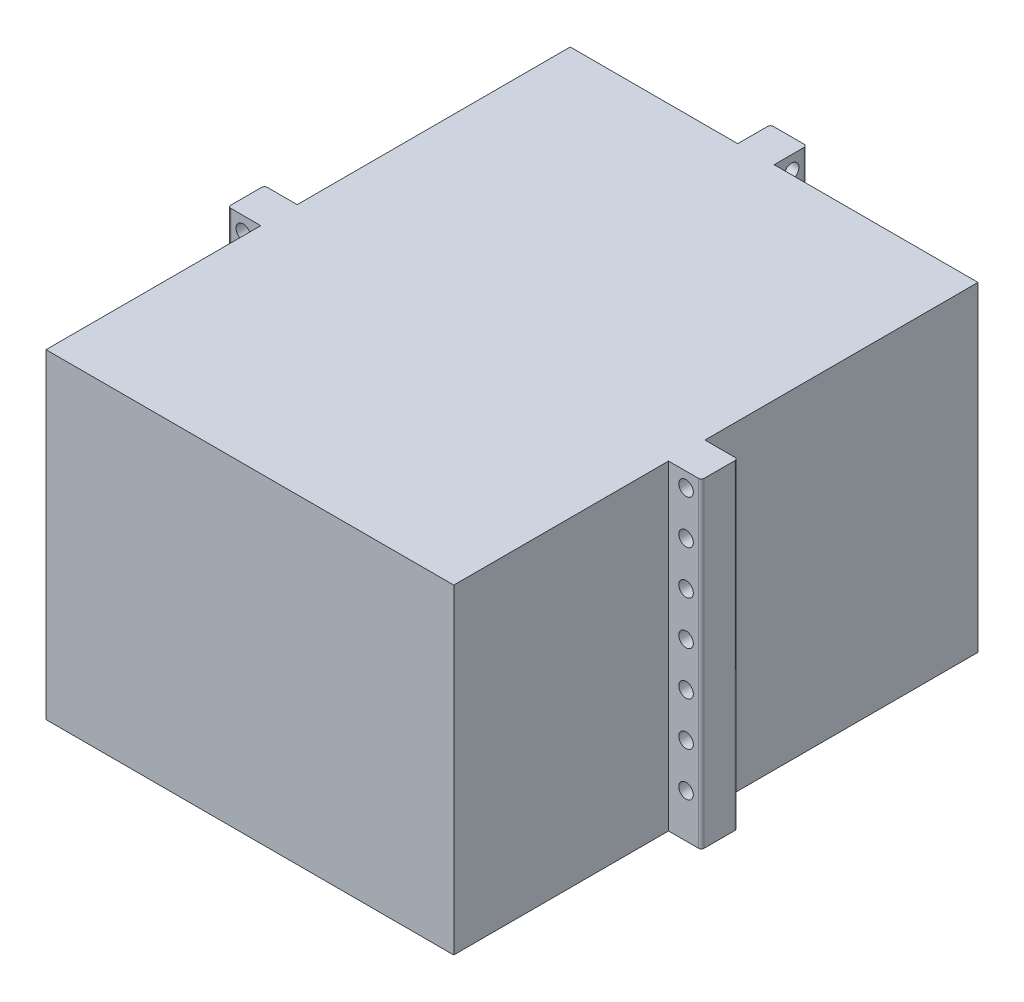
SolidWorks part; units mm, degrees
material "6061 Alloy"
ref_plane "Front Plane" through (0, 0, 0) normal (0, 0, 1) x (1, 0, 0)
ref_plane "Top Plane" through (0, 0, 0) normal (0, 1, 0) x (1, 0, 0)
ref_plane "Right Plane" through (0, 0, 0) normal (1, 0, 0) x (0, 0, -1)
sketch "Sketch1" plane through (0, 0, 0) normal (0, 1, 0) x (1, 0, 0)
  line L0 (-31.75, -228.6) -> (31.75, -228.6) construction
  line L1 (177.8, 228.6) -> (-177.8, 228.6) construction
  line L2 (177.8, 228.6) -> (177.8, -228.6) construction
  line L3 (177.8, -228.6) -> (-177.8, -228.6) construction
  line L4 (-177.8, 228.6) -> (-177.8, -228.6) construction
  line L5 (177.8, 228.6) -> (-177.8, -228.6) construction
  line L6 (177.8, -228.6) -> (-177.8, 228.6) construction
  line L7 (-31.75, -228.6) -> (-31.75, -269.875) construction
  line L8 (31.75, -228.6) -> (31.75, -269.875) construction
  line L9 (-31.75, -269.875) -> (31.75, -269.875) construction
  line L10 (-177.8, -228.6) -> (-31.75, -228.6)
  line L11 (31.75, -228.6) -> (-31.75, -228.6)
  line L12 (0, 228.6) -> (-31.75, 228.6) construction
  line L13 (0, 228.6) -> (0, 257.175)
  line L14 (31.75, -228.6) -> (177.8, -228.6)
  line L15 (-31.75, 228.6) -> (-31.75, 257.175)
  line L16 (0, 257.175) -> (-31.75, 257.175)
  line L17 (-31.75, 228.6) -> (-177.8, 228.6)
  line L18 (0, 228.6) -> (177.8, 228.6)
  line L19 (-177.8, -9.525) -> (-206.375, -9.525)
  line L20 (-177.8, -9.525) -> (-177.8, -41.275) construction
  line L21 (-206.375, -9.525) -> (-206.375, -41.275)
  line L22 (-177.8, -41.275) -> (-206.375, -41.275)
  line L23 (177.8, -9.525) -> (177.8, -41.275) construction
  line L24 (177.8, -9.525) -> (206.375, -9.525)
  line L25 (177.8, -41.275) -> (206.375, -41.275)
  line L26 (206.375, -9.525) -> (206.375, -41.275)
  line L27 (-177.8, 228.6) -> (-177.8, -9.525)
  line L28 (-177.8, -41.275) -> (-177.8, -228.6)
  line L29 (177.8, -41.275) -> (177.8, -228.6)
  line L30 (177.8, -9.525) -> (177.8, 228.6)
  point P0 (0, 0)
  point P6 (192.0875, -9.525)
  point P13 (-15.875, 228.6)
  point P22 (192.0875, -41.275)
  point P25 (-192.0875, -41.275)
  dimension "D1" = 355.6
  dimension "D2" = 457.2
  dimension "D3" = 146.05
  dimension "D4" = 146.05
  dimension "D5" = 41.275
  dimension "D6" = 146.05
  dimension "D7" = 31.75
  dimension "D8" = 28.575
  dimension "D9" = 238.125
  dimension "D10" = 238.125
  dimension "D11" = 31.75
  dimension "D12" = 31.75
  dimension "D13" = 28.575
  dimension "D14" = 28.575
extrude "Boss-Extrude1" add sketch "Sketch1" along normal blind 279.4
ref_point "Point2"
ref_axis "Axis1" through (0, 139.7, 228.6) along (0, 1, 0)
sketch "Sketch2" plane through (0, 0, 41.275) normal (0, 0, 1) x (1, 0, 0)
  line L0 (-193.04, 279.4) -> (-193.04, 0) construction
  line L1 (-206.375, 279.4) -> (-177.8, 279.4) construction
  line L2 (-206.375, 0) -> (-177.8, 0) construction
  line L3 (-177.8, 279.4) -> (-177.8, 0) construction
  line L4 (0, 135.6782) -> (0, 345.0284)
  line L5 (0, 139.7) -> (0, 350.0578) construction
  line L6 (193.04, 279.4) -> (193.04, 0) construction
  circle A0 centre (-193.04, 38.1) radius 6.35
  circle A1 centre (-193.04, 76.2) radius 6.35
  circle A2 centre (-193.04, 114.3) radius 6.35
  circle A3 centre (-193.04, 152.4) radius 6.35
  circle A4 centre (-193.04, 190.5) radius 6.35
  circle A5 centre (-193.04, 228.6) radius 6.35
  circle A6 centre (-193.04, 266.7) radius 6.35
  circle A7 centre (193.04, 266.7) radius 6.35
  circle A8 centre (193.04, 228.6) radius 6.35
  circle A9 centre (193.04, 190.5) radius 6.35
  circle A10 centre (193.04, 152.4) radius 6.35
  circle A11 centre (193.04, 114.3) radius 6.35
  circle A12 centre (193.04, 76.2) radius 6.35
  circle A13 centre (193.04, 38.1) radius 6.35
  point P10 (-193.04, 53.7554)
  point P45 (193.04, 53.7554)
  dimension "D2" = 12.7
  dimension "D1" = 15.24
  dimension "D3" = 38.1
  dimension "D4" = 7
extrude "Cut-Extrude1" cut sketch "Sketch2" against normal blind 45.72 contours A6 | A5 | A3 | A4 | A2 | A1 | A0 | A7 | A8 | A9 | A10 | A11 | A12 | A13
sketch "Sketch3" plane through (-31.75, 0, 0) normal (-1, 0, 0) x (0, 0, 1)
  line L0 (-243.84, 279.4) -> (-243.84, 0) construction
  line L1 (-257.175, 279.4) -> (-228.6, 279.4) construction
  line L2 (-257.175, 0) -> (-228.6, 0) construction
  line L3 (-228.6, 279.4) -> (-228.6, 0) construction
  circle A0 centre (-243.84, 38.1) radius 6.35
  circle A1 centre (-243.84, 76.2) radius 6.35
  circle A2 centre (-243.84, 114.3) radius 6.35
  circle A3 centre (-243.84, 152.4) radius 6.35
  circle A4 centre (-243.84, 190.5) radius 6.35
  circle A5 centre (-243.84, 228.6) radius 6.35
  circle A6 centre (-243.84, 266.7) radius 6.35
  point P10 (-243.84, 53.0999)
  dimension "D2" = 12.7
  dimension "D1" = 15.24
  dimension "D3" = 38.1
  dimension "D4" = 7
extrude "Cut-Extrude2" cut sketch "Sketch3" against normal blind 45.72
fillet "Fillet1" radius 2.54 6 edges at (206.375, 139.7, 41.275) (206.375, 139.7, 9.525) (0, 139.7, -257.175) (-31.75, 139.7, -257.175) (-206.375, 139.7, 41.275) (-206.375, 139.7, 9.525)
